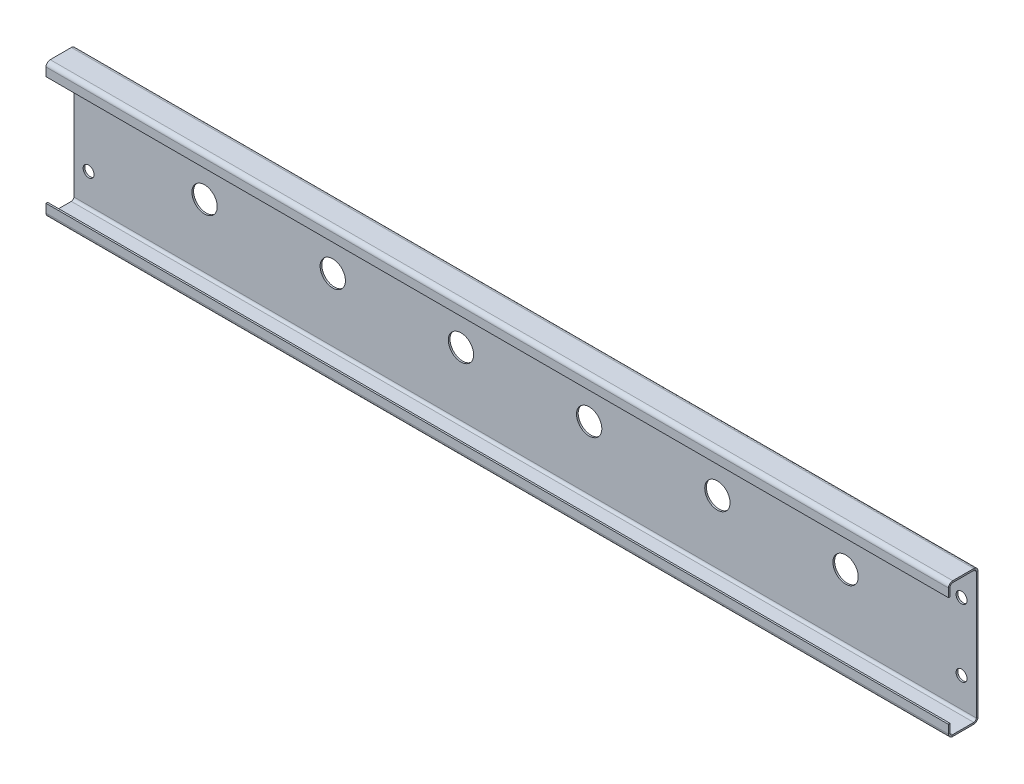
SolidWorks part; units mm, degrees
note: The reader was unsure of these and kept them because the rebuilt part matched: thickness of "Base-Flange1", "Edge-Flange1", "Edge-Flange2", "Sheet-Metal1", "Sheet-Metal2", "Sheet-Metal3", "Sheet-Metal4", "Sheet-Metal5", "Sheet-Metal6"; flange length of "Edge-Flange1", "Edge-Flange2".
material "Galvanized Steel"
ref_plane "Front Plane" through (0, 0, 0) normal (0, 0, 1) x (1, 0, 0)
ref_plane "Top Plane" through (0, 0, 0) normal (0, 1, 0) x (1, 0, 0)
ref_plane "Right Plane" through (0, 0, 0) normal (1, 0, 0) x (0, 0, -1)
sketch "Sketch1" plane through (0, 0, 0) normal (0, 0, 1) x (1, 0, 0)
  line L1 (-535, -80) -> (535, -80)
  line L2 (-535, -80) -> (-535, 80)
  line L3 (-535, 80) -> (535, 80)
  line L4 (535, -80) -> (535, 80)
  line L5 (-535, -80) -> (535, 80) construction
  line L6 (-535, 80) -> (535, -80) construction
  point P0 (0, 0)
  dimension "D1" = 1070
  dimension "D2" = 160
base flange "Base-Flange1" sketch "Sketch1" thickness 2 reverse thickness direction no parameters "D1"=3
edge flange "Edge-Flange1" sketch "Sketch10" flange profiles "Sketch10", "Sketch11" flange angle 90 flange length 35 flange position material inside bend radius 3 thickness 2 relief rectangular parameters "D6"=10, "D8"=1
sketch "Sketch10" plane through (0, 80, 0) normal (0, 1, 0) x (-1, 0, 0)
  line L0 (-535, 0) -> (535, 0) construction
  line L1 (-535, 0) -> (535, 0)
  line L2 (-535, 0) -> (-535, 33)
  line L3 (-535, 33) -> (535, 33)
  line L4 (535, 33) -> (535, 0)
sketch "Sketch11" plane through (0, -80, 0) normal (0, -1, 0) x (1, 0, 0)
  line L0 (-535, 0) -> (535, 0) construction
  line L1 (-535, 0) -> (535, 0)
  line L2 (-535, 0) -> (-535, 33)
  line L3 (-535, 33) -> (535, 33)
  line L4 (535, 33) -> (535, 0)
bend "EdgeBend1" bend radius 3 bend angle 90 parameters "D5"=1
bend "EdgeBend2" bend radius 3 bend angle 90 parameters "D5"=2
edge flange "Edge-Flange2" sketch "Sketch16" flange profiles "Sketch16", "Sketch17" flange angle 90 flange length 15 flange position material inside bend radius 3 thickness 2 relief rectangular parameters "D6"=10, "D8"=1
sketch "Sketch16" plane through (0, -78, 33) normal (0, 0, 1) x (1, 0, 0)
  line L0 (535, 0) -> (-535, 0) construction
  line L1 (535, 0) -> (-535, 0)
  line L2 (-535, 0) -> (-535, 13)
  line L3 (-535, 13) -> (535, 13)
  line L4 (535, 13) -> (535, 0)
sketch "Sketch17" plane through (0, 78, 33) normal (0, 0, 1) x (-1, 0, 0)
  line L0 (535, 0) -> (-535, 0) construction
  line L1 (535, 0) -> (-535, 0)
  line L2 (-535, 0) -> (-535, 13)
  line L3 (-535, 13) -> (535, 13)
  line L4 (535, 13) -> (535, 0)
bend "EdgeBend3" bend radius 3 bend angle 90 parameters "D5"=3
bend "EdgeBend4" bend radius 3 bend angle 90 parameters "D5"=4
sketch "Sketch18" plane through (0, 0, 0) normal (0, 0, 1) x (1, 0, 0)
  line L0 (-535, 75) -> (-535, -75) construction
  line L1 (535, -80) -> (-535, -80) construction
  line L2 (535, -75) -> (535, 75) construction
  circle A0 centre (-517.5, -40) radius 6.5
  circle A1 centre (-517.5, 40) radius 6.5
  circle A2 centre (517.5, 40) radius 6.5
  circle A3 centre (517.5, -40) radius 6.5
  dimension "D1" = 13
  dimension "D2" = 17.5
  dimension "D3" = 13
  dimension "D4" = 80
  dimension "D5" = 40
  dimension "D6" = 80
  dimension "D7" = 17.5
extrude "Cut-Extrude1" cut sketch "Sketch18" against normal blind 10 contours A1 | A0 | A3 | A2 normal cut yes
sketch "Sketch19" plane through (0, 0, 0) normal (0, 0, 1) x (1, 0, 0)
  line L0 (535, -75) -> (535, 75) construction
  circle A0 centre (380, 0) radius 15
  dimension "D1" = 30
  dimension "D2" = 155
extrude "Cut-Extrude2" cut sketch "Sketch19" against normal through all both and the other way through all normal cut yes
pattern_linear "LPattern1" count 6 spacing 152 along (-1, 0, 0) of "Cut-Extrude2"
sketch "Bend-Lines1" [suppressed] plane through (0, 0, 0) normal (0, 1, 0) x (1, 0, 0)
sketch "Bounding-Box1" [suppressed] plane through (0, 0, 0) normal (0, 1, 0) x (1, 0, 0)
sheet metal parameters "Sheet-Metal1" thickness 2 parameters "D1"=3
flat pattern "Flat-Pattern1" [suppressed]
sketch "Bend-Lines2" plane through (0, 0, 0) normal (0, 1, 0) x (1, 0, 0)
sketch3d "Bounding-Box2" [suppressed]
  line L0 (710, -80, 0) -> (-710, -80, 0) construction
  line L1 (710, 80, 0) -> (-710, 80, 0) construction
  line L2 (710, -80, 0) -> (710, 80, 0) construction
  line L3 (-710, -80, 0) -> (-710, 80, 0) construction
sheet metal parameters "Sheet-Metal2" thickness 2 parameters "D1"=3, "D7"=1.5
flat pattern "Flat-Pattern1"
sketch "Bend-Lines2" plane through (0, 0, 0) normal (0, 0, 1) x (1, 0, 0)
  line L0 (-710, -78.4452) -> (710, -78.4452) construction
  line L1 (710, 78.4452) -> (-710, 78.4452) construction
  line L2 (-710, -78.4452) -> (710, -78.4452) construction
  line L3 (710, 78.4452) -> (-710, 78.4452) construction
sketch3d "Bounding-Box2" [suppressed]
  line L0 (-710, -111.8905, 0) -> (710, -111.8905, 0) construction
  line L1 (-710, 111.8905, 0) -> (710, 111.8905, 0) construction
  line L2 (-710, -111.8905, 0) -> (-710, 111.8905, 0) construction
  line L3 (710, -111.8905, 0) -> (710, 111.8905, 0) construction
bend of the flat pattern "Flatten-<EdgeBend1>1"
bend of the flat pattern "Flatten-<EdgeBend2>1"
sheet metal parameters "Sheet-Metal3" thickness 2 parameters "D1"=3, "D7"=1.5
flat pattern "Flat-Pattern1"
sketch "Bend-Lines2" plane through (0, 0, 0) normal (0, 0, 1) x (1, 0, 0)
  line L0 (-710, -78.4452) -> (710, -78.4452) construction
  line L1 (710, 78.4452) -> (-710, 78.4452) construction
  line L2 (-710, -78.4452) -> (710, -78.4452) construction
  line L3 (710, 78.4452) -> (-710, 78.4452) construction
  line L4 (710, 110.3357) -> (-710, 110.3357) construction
  line L5 (-710, -110.3357) -> (710, -110.3357) construction
  line L6 (710, 110.3357) -> (-710, 110.3357) construction
  line L7 (-710, -110.3357) -> (710, -110.3357) construction
sketch3d "Bounding-Box2" [suppressed]
  line L0 (-710, -123.781, 0) -> (710, -123.781, 0) construction
  line L1 (-710, 123.781, 0) -> (710, 123.781, 0) construction
  line L2 (-710, -123.781, 0) -> (-710, 123.781, 0) construction
  line L3 (710, -123.781, 0) -> (710, 123.781, 0) construction
bend of the flat pattern "Flatten-<EdgeBend1>1"
bend of the flat pattern "Flatten-<EdgeBend2>1"
bend of the flat pattern "Flatten-<EdgeBend3>1"
bend of the flat pattern "Flatten-<EdgeBend4>1"
sheet metal parameters "Sheet-Metal4" thickness 2 parameters "D1"=3, "D7"=1.5
flat pattern "Flat-Pattern1"
sketch "Bend-Lines2" plane through (0, 0, 0) normal (0, 0, 1) x (1, 0, 0)
  line L0 (-710, -78.4452) -> (710, -78.4452) construction
  line L1 (710, 78.4452) -> (-710, 78.4452) construction
  line L2 (-710, -78.4452) -> (710, -78.4452) construction
  line L3 (710, 78.4452) -> (-710, 78.4452) construction
  line L4 (710, 110.3357) -> (-710, 110.3357) construction
  line L5 (-710, -110.3357) -> (710, -110.3357) construction
  line L6 (710, 110.3357) -> (-710, 110.3357) construction
  line L7 (-710, -110.3357) -> (710, -110.3357) construction
sketch3d "Bounding-Box2" [suppressed]
  line L0 (-710, -123.781, 0) -> (710, -123.781, 0) construction
  line L1 (-710, 123.781, 0) -> (710, 123.781, 0) construction
  line L2 (-710, -123.781, 0) -> (-710, 123.781, 0) construction
  line L3 (710, -123.781, 0) -> (710, 123.781, 0) construction
bend of the flat pattern "Flatten-<EdgeBend1>1"
bend of the flat pattern "Flatten-<EdgeBend2>1"
bend of the flat pattern "Flatten-<EdgeBend3>1"
bend of the flat pattern "Flatten-<EdgeBend4>1"
sheet metal parameters "Sheet-Metal5" thickness 2 parameters "D1"=3, "D7"=1.5
flat pattern "Flat-Pattern1"
sketch "Bend-Lines2" plane through (0, 0, 0) normal (0, 0, 1) x (1, 0, 0)
  line L0 (-710, -78.4452) -> (710, -78.4452) construction
  line L1 (710, 78.4452) -> (-710, 78.4452) construction
  line L2 (-710, -78.4452) -> (710, -78.4452) construction
  line L3 (710, 78.4452) -> (-710, 78.4452) construction
  line L4 (710, 110.3357) -> (-710, 110.3357) construction
  line L5 (-710, -110.3357) -> (710, -110.3357) construction
  line L6 (710, 110.3357) -> (-710, 110.3357) construction
  line L7 (-710, -110.3357) -> (710, -110.3357) construction
sketch3d "Bounding-Box2" [suppressed]
  line L0 (-710, -123.781, 0) -> (710, -123.781, 0) construction
  line L1 (-710, 123.781, 0) -> (710, 123.781, 0) construction
  line L2 (-710, -123.781, 0) -> (-710, 123.781, 0) construction
  line L3 (710, -123.781, 0) -> (710, 123.781, 0) construction
bend of the flat pattern "Flatten-<EdgeBend1>1"
bend of the flat pattern "Flatten-<EdgeBend2>1"
bend of the flat pattern "Flatten-<EdgeBend3>1"
bend of the flat pattern "Flatten-<EdgeBend4>1"
sheet metal parameters "Sheet-Metal6" thickness 2 parameters "D1"=3, "D7"=1.5
flat pattern "Flat-Pattern1"
sketch "Bend-Lines2" plane through (0, 0, 0) normal (0, 0, 1) x (1, 0, 0)
  line L0 (-535, -78.1416) -> (535, -78.1416) construction
  line L1 (535, 78.1416) -> (-535, 78.1416) construction
  line L2 (-535, -78.1416) -> (535, -78.1416) construction
  line L3 (535, 78.1416) -> (-535, 78.1416) construction
  line L4 (535, 109.4248) -> (-535, 109.4248) construction
  line L5 (-535, -109.4248) -> (535, -109.4248) construction
  line L6 (535, 109.4248) -> (-535, 109.4248) construction
  line L7 (-535, -109.4248) -> (535, -109.4248) construction
sketch3d "Bounding-Box2" [suppressed]
  line L0 (-535, -122.5664, 0) -> (535, -122.5664, 0) construction
  line L1 (-535, 122.5664, 0) -> (535, 122.5664, 0) construction
  line L2 (-535, -122.5664, 0) -> (-535, 122.5664, 0) construction
  line L3 (535, -122.5664, 0) -> (535, 122.5664, 0) construction
bend of the flat pattern "Flatten-<EdgeBend1>1"
bend of the flat pattern "Flatten-<EdgeBend2>1"
bend of the flat pattern "Flatten-<EdgeBend3>1"
bend of the flat pattern "Flatten-<EdgeBend4>1"
